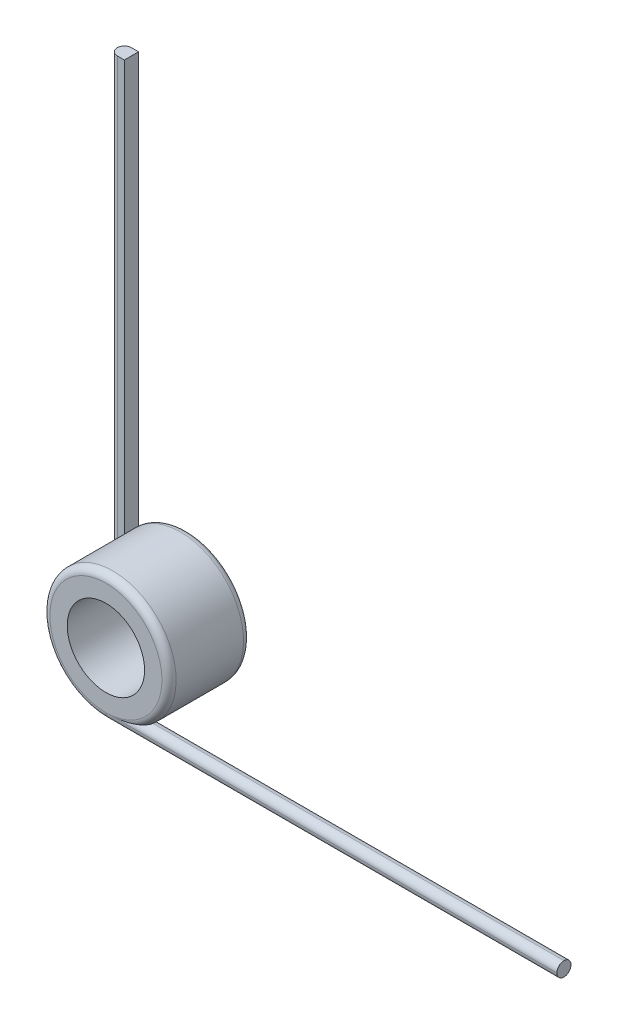
SolidWorks part; units mm, degrees
ref_plane "Front Plane" through (0, 0, 0) normal (0, 0, 1) x (1, 0, 0)
ref_plane "Top Plane" through (0, 0, 0) normal (0, 1, 0) x (1, 0, 0)
ref_plane "Right Plane" through (0, 0, 0) normal (1, 0, 0) x (0, 0, -1)
sketch "Sketch1" plane through (0, 0, 0) normal (0, 0, 1) x (1, 0, 0)
  circle A0 centre (0, 0) radius 7.112
  circle A1 centre (0, 0) radius 4.3561
  dimension "D1" = 14.224
  dimension "D2" = 8.7122
extrude "Boss-Extrude1" add sketch "Sketch1" along normal blind 9.1948
sketch "Sketch2" plane through (0, 0, 9.1948) normal (0, 0, 1) x (1, 0, 0)
  line L0 (-7.112, 0) -> (-7.112, 50.8)
  line L1 (-7.112, 50.8) -> (-5.5118, 50.8)
  line L2 (-5.5118, 50.8) -> (-5.5118, 4.4945)
  line L3 (0, 0) -> (0, -14.6657) construction
  circle A0 centre (0, 0) radius 7.112 construction
  arc A1 (-5.5118, 4.4945) -> (-7.112, 0) centre (0, 0) ccw
  dimension "D1" = 50.8
  dimension "D2" = 1.6002
  dimension "D3" = 180
extrude "Boss-Extrude2" add sketch "Sketch2" along normal blind 1.6002 from surface starting at face at (7.112, 0, 0)
fillet "Fillet1" radius 0.8001 3 edges at (-7.112, 25.4, 1.6002) (-7.112, 25.4, 0) (6.7, -2.3854, 0)
sketch "Sketch4" plane through (0, 0, 0) normal (0, 0, -1) x (-1, 0, 0)
  line L0 (0, -7.112) -> (-50.8, -7.112)
  line L1 (-50.8, -7.112) -> (-50.8, -5.5118)
  line L2 (-50.8, -5.5118) -> (-4.4945, -5.5118)
  circle A0 centre (0, 0) radius 7.112 construction
  arc A1 (-4.4945, -5.5118) -> (0, -7.112) centre (0, 0) ccw
  dimension "D1" = 1.6002
  dimension "D2" = 50.8
extrude "Boss-Extrude4" add sketch "Sketch4" along normal blind 1.6002 from surface starting at face at (7.112, 0, 9.1948)
fillet "Fillet2" radius 0.8001 5 edges at (25.4, -7.112, 7.5946) (27.6473, -5.5118, 7.5946) (25.4, -7.112, 9.1948) (27.6473, -5.5118, 9.1948) (-2.3854, 6.7, 9.1948)
equation "\"diam\" = .063"
equation "\"shaft\" = .343"
equation "\"od\" = .56in"
equation "\"length\" = .362"
equation "\"D1@Sketch1\"=\"od\""
equation "\"D2@Sketch1\"=\"shaft\""
equation "\"coils\"= 8"
equation "\"D1@Boss-Extrude1\"=\"length\""
equation "\"D1@Boss-Extrude2\"=\"diam\""
equation "\"D2@Sketch2\"=\"diam\""
equation "\"arm\"= 2"
equation "\"D1@Sketch2\"=\"arm\""
equation "\"D2@Sketch4\"=\"arm\""
equation "\"D1@Sketch4\"=\"diam\""
equation "\"D1@Boss-Extrude4\"=\"diam\""
equation "\"D1@Fillet2\"=\"diam\"/2"
equation "\"D1@Fillet1\"=\"diam\"/2"
